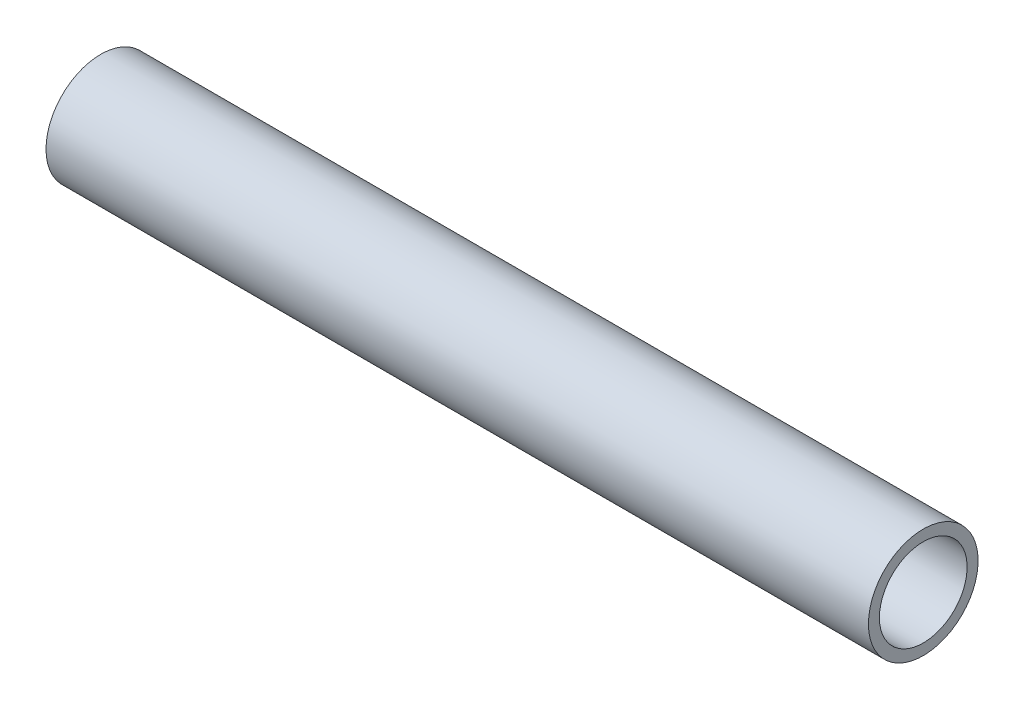
SolidWorks part; units mm, degrees
material "PC High Viscosity"
ref_plane "Front Plane" through (0, 0, 0) normal (0, 0, 1) x (1, 0, 0)
ref_plane "Top Plane" through (0, 0, 0) normal (0, 1, 0) x (1, 0, 0)
ref_plane "Right Plane" through (0, 0, 0) normal (1, 0, 0) x (0, 0, -1)
sketch "Sketch1" plane through (0, 0, 0) normal (1, 0, 0) x (0, 0, -1)
  circle A0 centre (0, 0) radius 15.875
  dimension "D1" = 31.75
extrude "Extrude-Thin1" add sketch "Sketch1" along normal mid plane 238.0932 thin thin type one direction reverse wall 3.175
